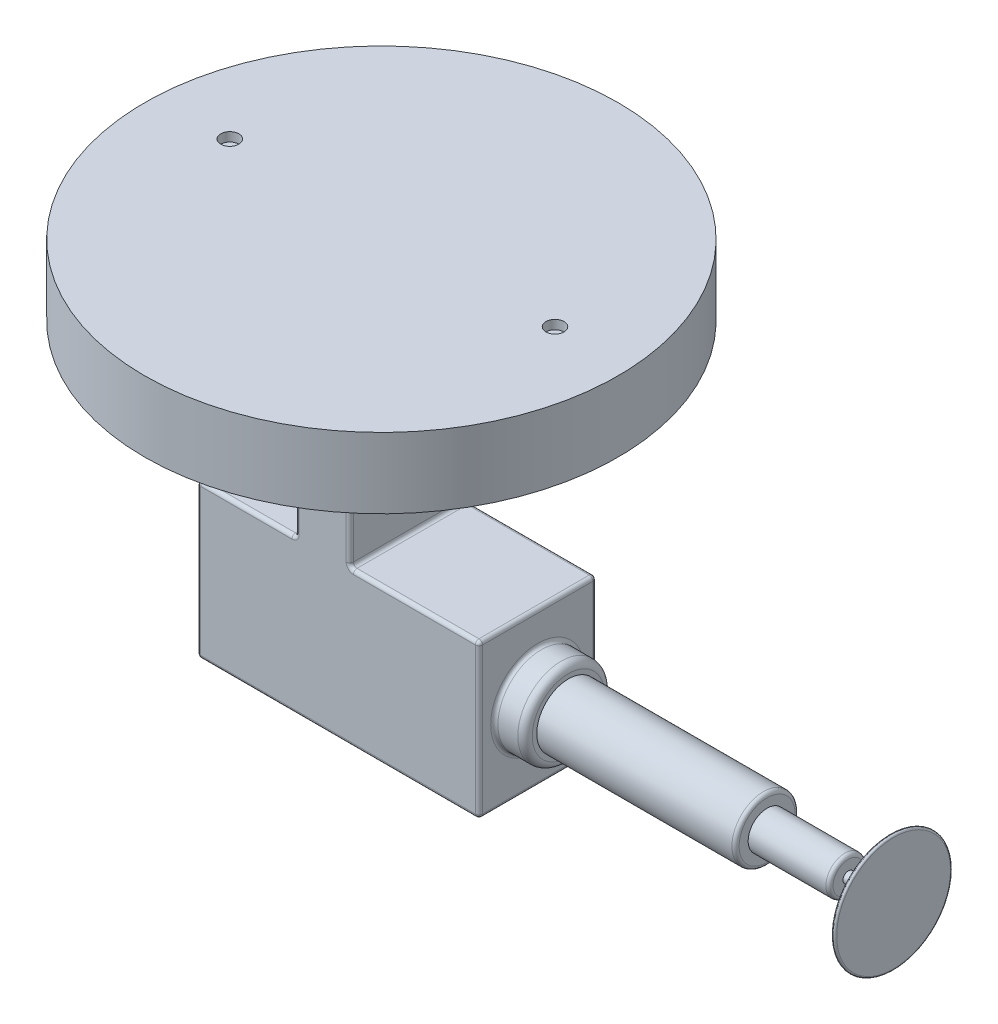
SolidWorks part; units mm, degrees
ref_plane "Front Plane" through (0, 0, 0) normal (0, 0, 1) x (1, 0, 0)
ref_plane "Top Plane" through (0, 0, 0) normal (0, 1, 0) x (1, 0, 0)
ref_plane "Right Plane" through (0, 0, 0) normal (1, 0, 0) x (0, 0, -1)
sketch "Sketch1" plane through (0, 0, 0) normal (0, 1, 0) x (1, 0, 0)
  line L1 (0, 0) -> (156, 0)
  line L2 (0, 0) -> (0, 65)
  line L3 (0, 65) -> (156, 65)
  line L4 (156, 0) -> (156, 65)
  dimension "D1" = 156
  dimension "D2" = 65
extrude "Boss-Extrude1" add sketch "Sketch1" along normal blind 85
sketch "Sketch2" plane through (156, 0, 0) normal (1, 0, 0) x (0, 0, -1)
  line L0 (0, 85) -> (0, 0) construction
  line L1 (0, 0) -> (65, 0) construction
  circle A0 centre (32.5, 42.5) radius 24
  point P2 (0, 42.5)
  dimension "D1" = 48
  dimension "D3" = 42.5
  dimension "D2" = 32.5
sketch "Sketch5" plane through (0, 85, 0) normal (0, 1, 0) x (1, 0, 0)
  line L0 (156, 65) -> (0, 65) construction
  line L1 (54.5, 65) -> (84.5, 65)
  line L2 (54.5, 65) -> (54.5, 0)
  line L3 (54.5, 0) -> (84.5, 0)
  line L4 (84.5, 65) -> (84.5, 0)
  line L5 (0, 0) -> (156, 0) construction
  line L6 (0, 65) -> (0, 0) construction
  dimension "D1" = 30
  dimension "D2" = 54.5
extrude "Boss-Extrude4" add sketch "Sketch5" along normal blind 95
sketch "Sketch6" plane through (0, 180, 0) normal (0, 1, 0) x (1, 0, 0)
  circle A0 centre (69.5, 32.5) radius 131
  dimension "D1" = 262
extrude "Boss-Extrude5" add sketch "Sketch6" along normal blind 39
sketch "Sketch7" plane through (0, 219, 0) normal (0, 1, 0) x (-1, 0, 0)
  circle A0 centre (20.5, -38.588) radius 5
  circle A1 centre (-69.5, -32.5) radius 131 construction
  circle A2 centre (-159.5, -38.588) radius 5
  dimension "D1" = 10
  dimension "D2" = 90
  dimension "D3" = 90
extrude "Cut-Extrude3" cut sketch "Sketch7" against normal blind 5
fillet "Fillet10" radius 2 1 edges at (0, 42.5, 0)
fillet "Fillet11" radius 2 12 edges at (79, 0, 0) (0, 0, -33.5) (0, 85, -33.5) (0, 42.5, -65) (0.5858, 0, -0.5858) (0.5858, 85, -0.5858)
fillet "Fillet12" radius 2 11 edges at (79, 0, -65) (156, 0, -33.5) (0.5858, 0.5858, -64.4142) (156, 43.5, 0) (156, 0.5858, -0.5858) (85.0858, 85.5858, -65) (85.0858, 85.5858, 0)
fillet "Fillet16" radius 2 5 edges at (155.4142, 84.4142, -0.5858) (155.4142, 0.5858, -64.4142) (156, 42.5, -65) (156, 84.4142, -64.4142) (156, 85, -32.5)
extrude "Boss-Extrude6" add sketch "Sketch2" along normal blind 17
sketch "Sketch8" plane through (173, 0, 0) normal (1, 0, 0) x (0, 0, -1)
  circle A0 centre (32.5, 42.5) radius 17.5
  dimension "D1" = 35
extrude "Boss-Extrude7" add sketch "Sketch8" along normal blind 110
sketch "Sketch9" plane through (283, 0, 0) normal (1, 0, 0) x (0, 0, -1)
  circle A0 centre (32.5, 42.5) radius 10.5
  dimension "D1" = 21
extrude "Boss-Extrude8" add sketch "Sketch9" along normal blind 45
sketch "Sketch10" plane through (328, 0, 0) normal (1, 0, 0) x (0, 0, -1)
  circle A0 centre (32.5, 42.5) radius 3
  dimension "D1" = 6
extrude "Boss-Extrude9" add sketch "Sketch10" along normal blind 23
sketch "Sketch11" plane through (351, 0, 0) normal (1, 0, 0) x (0, 0, -1)
  circle A0 centre (32.5, 42.5) radius 32.5
  dimension "D1" = 65
extrude "Boss-Extrude10" add sketch "Sketch11" along normal blind 2
fillet "Fillet17" radius 2 3 edges at (328, 42.5, -43) (283, 42.5, -50) (156, 42.5, -8.5)
fillet "Fillet18" radius 4 1 edges at (173, 42.5, -56.5)
fillet "Fillet19" radius 1 2 edges at (353, 42.5, -65) (351, 42.5, -65)
